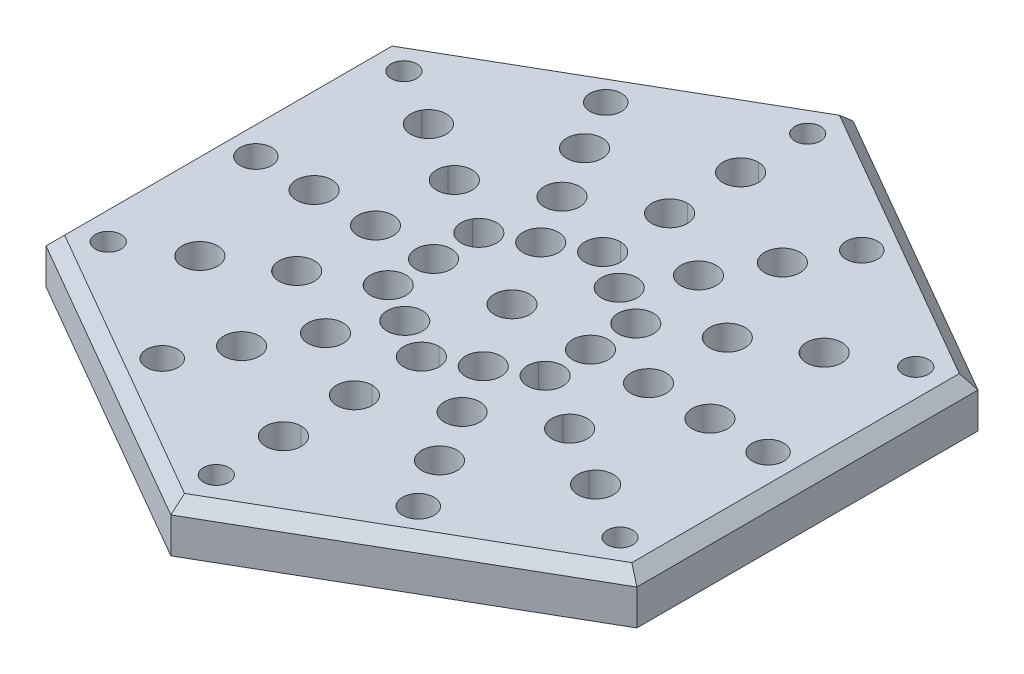
SolidWorks part; units mm, degrees
note: '?' marks a value the reader was unsure of.
ref_plane "前基準面" through (0, 0, 0) normal (0, 0, 1) x (1, 0, 0)
ref_plane "上基準面" through (0, 0, 0) normal (0, 1, 0) x (1, 0, 0)
ref_plane "右基準面" through (0, 0, 0) normal (1, 0, 0) x (0, 0, -1)
sketch "草圖1" plane through (0, 0, 0) normal (0, 1, 0) x (1, 0, 0)
  line L1 (75, 43.3013) -> (0, 86.6025)
  line L2 (0, 86.6025) -> (-75, 43.3013)
  line L3 (-75, 43.3013) -> (-75, -43.3013)
  line L4 (-75, -43.3013) -> (0, -86.6025)
  line L5 (0, -86.6025) -> (75, -43.3013)
  line L6 (75, -43.3013) -> (75, 43.3013)
  circle A0 centre (0, 0) radius 75 construction
  dimension "D1" = 150
extrude "填料-伸長1" add sketch "草圖1" along normal blind 12
chamfer "導角1" distance 3 angle 45 6 edges at (37.5, 12, 64.9519) (75, 12, 0) (37.5, 12, -64.9519) (-37.5, 12, -64.9519) (-75, 12, 0) (-37.5, 12, 64.9519)
sketch "草圖2" plane through (0, 0, 0) normal (0, -1, 0) x (1, 0, 0)
  circle A0 centre (65, -37.5) radius 3.25
  point P2 (0, 0)
  dimension "D1" = 6.5
  dimension "D3" = 37.5
  dimension "D2" = 65
extrude "除料-伸長1" cut sketch "草圖2" against normal through all
ref_axis "基準軸1" through (0, 0, 0) along (0, 1, 0)?
pattern_circular "環狀複製排列1" count 6 over 360 about axis through (0, 0, 0) along (0, 1, 0) of "除料-伸長1"
sketch "草圖4" plane through (0, 0, 0) normal (0, -1, 0) x (1, 0, 0)
  circle A0 centre (65, 0) radius 4
  point P2 (0, 0)
  dimension "D1" = 8
  dimension "D2" = 65
extrude "除料-伸長2" cut sketch "草圖4" against normal through all
pattern_circular "環狀複製排列2" count 6 over 360 about axis through (0, 0, 0) along (0, 1, 0) of "除料-伸長2"
sketch "草圖5" plane through (0, 0, 0) normal (0, -1, 0) x (1, 0, 0)
  line L0 (0, 0) -> (64.976, 37.5417) construction
  circle A0 centre (0, 0) radius 4.5
  circle A1 centre (0, 23.0064) radius 4.5
  circle A2 centre (0, 40.0111) radius 4.5
  circle A3 centre (0, 58.0161) radius 4.5
  circle A4 centre (19.9204, 11.5096) radius 4.5
  circle A5 centre (34.6442, 20.0167) radius 4.5
  circle A6 centre (50.2341, 29.0241) radius 4.5
  point P10 (0, 0)
  point P11 (0, 0)
  point P17 (0, 0)
  point P18 (0, 0)
  dimension "D1" = 9
  dimension "D3" = 23
  dimension "D4" = 40
  dimension "D2" = 2
  dimension "D5" = 58
extrude "除料-伸長3" cut sketch "草圖5" against normal through all contours A0
sketch "草圖9" plane through (0, 0, 0) normal (0, -1, 0) x (1, 0, 0)
  line L0 (0, 0) -> (32.5, 56.2917) construction
  line L1 (0, 23.0064) -> (19.9204, 11.5096) construction
  line L2 (0, 40.0111) -> (34.6442, 20.0167) construction
  line L4 (0, 58.0161) -> (50.2341, 29.0241) construction
  circle A0 centre (0, 0) radius 4.5
  circle A1 centre (34.6442, 20.0167) radius 4.5
  circle A2 centre (34.6442, 20.0167) radius 4.5
  circle A3 centre (19.9204, 11.5096) radius 4.5
  circle A4 centre (19.9204, 11.5096) radius 4.5
  circle A5 centre (0, 58.0161) radius 4.5
  circle A6 centre (0, 58.0161) radius 4.5
  circle A7 centre (0, 40.0111) radius 4.5
  circle A8 centre (0, 40.0111) radius 4.5
  circle A9 centre (0, 23.0064) radius 4.5
  circle A10 centre (0, 23.0064) radius 4.5
  circle A11 centre (0, 0) radius 4.5
  circle A12 centre (0, 0) radius 4.5
  circle A13 centre (50.2341, 29.0241) radius 4.5
  circle A14 centre (50.2341, 29.0241) radius 4.5
  circle A15 centre (9.9602, 17.258) radius 4.5
  circle A16 centre (17.3269, 30.0111) radius 4.5
  circle A17 centre (25.1171, 43.5201) radius 4.5
  circle A18 centre (22.4069, 33.1485) radius 4.5 [skipped]
  circle A19 centre (32.4899, 48.0653) radius 4.5 [skipped]
  circle A20 centre (12.8839, 19.0604) radius 4.5 [skipped]
  point P28 (17.3221, 30.0139)
  point P29 (14.4602, 24.2386)
  dimension "D1" = 0
  dimension "D2" = 0
  dimension "D3" = 0
  dimension "D4" = 0
  dimension "D5" = 0
  dimension "D6" = 0
  dimension "D7" = 0
  dimension "D8" = 2
extrude "除料-伸長5" cut sketch "草圖9" against normal through all contours A10 | A15 | A4 | A2 | A14 | A17 | A16 | A8 | A6
pattern_circular "環狀複製排列3" count 6 over 360 about axis through (0, 0, 0) along (0, 1, 0) of "除料-伸長5"
